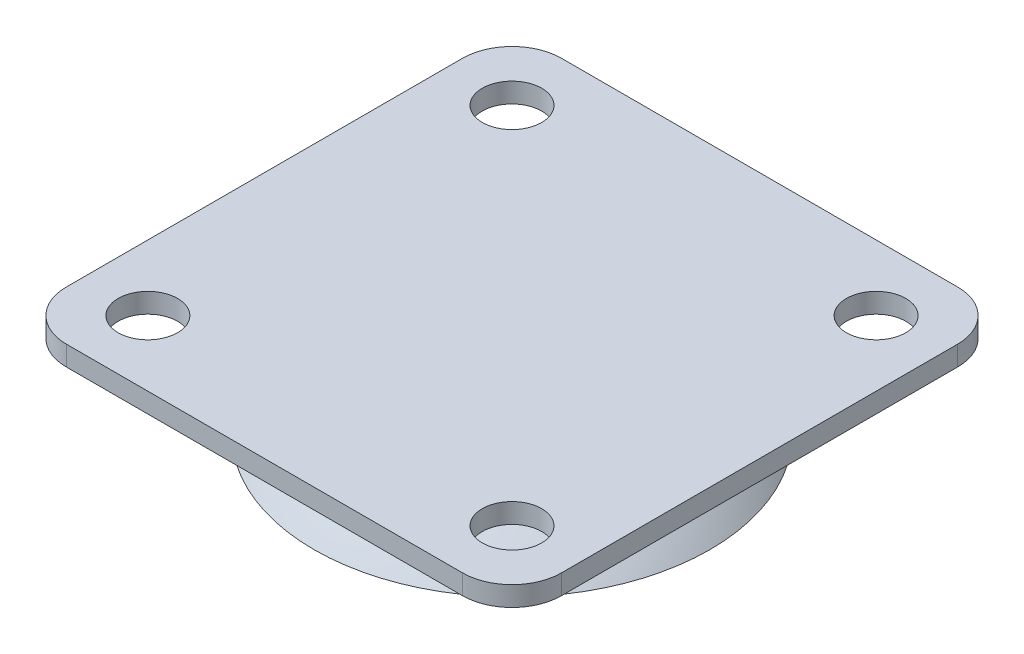
SolidWorks part; units mm, degrees
material "Chromium Copper, UNS C18200"
ref_plane "Front Plane" through (0, 0, 0) normal (0, 0, 1) x (1, 0, 0)
ref_plane "Top Plane" through (0, 0, 0) normal (0, 1, 0) x (1, 0, 0)
ref_plane "Right Plane" through (0, 0, 0) normal (1, 0, 0) x (0, 0, -1)
sketch "Sketch1" plane through (0, 0, 0) normal (0, 1, 0) x (1, 0, 0)
  line L0 (0, 37.0869) -> (0, -44.714) construction
  line L1 (-25, 25) -> (25, 25)
  line L2 (-25, 25) -> (-25, -25)
  line L3 (-25, -25) -> (25, -25)
  line L4 (25, 25) -> (25, -25)
  line L5 (-25, 25) -> (25, -25) construction
  line L6 (-25, -25) -> (25, 25) construction
  line L7 (28.9831, 0) -> (-36.8008, 0) construction
  circle A0 centre (18.3848, 18.3848) radius 3
  circle A1 centre (-18.3848, 18.3848) radius 3
  circle A2 centre (18.3848, -18.3848) radius 3
  circle A3 centre (-18.3848, -18.3848) radius 3
  point P0 (0, 0)
  dimension "D3" = 6
  dimension "D1" = 50
  dimension "D2" = 50
  dimension "D4" = 26
extrude "Boss-Extrude1" add sketch "Sketch1" along normal blind 2
sketch "Sketch2" plane through (0, 0, 0) normal (0, 0, 1) x (1, 0, 0)
  line L0 (0, 10.006) -> (0, -2.02) construction
  line L1 (0, 0) -> (0, -2.02)
  line L2 (20, -8.4681) -> (17.1604, -8.4681)
  line L3 (0, -2.9806) -> (0, -16.3725) construction
  line L4 (1.9993, -2.0726) -> (1.9993, -2.0726)
  line L5 (15.679, -7.1244) -> (15.679, -7.1244)
  line L6 (0, -2.02) -> (1.9993, -2.0726)
  line L7 (15.679, -7.1244) -> (17.1604, -8.4681)
  spline S0 degree 2 poles (0, 0) (12.4384, -0.0796) (20, -8.4681) knots 0 0 0 1 1 1
  spline S1 degree 1 poles (1.9993, -2.0726) (15.679, -7.1244) knots 0 0 1 1 construction
  spline S2 degree 3 poles (1.9993, -2.0726) (2.666, -2.1173) (4.014, -2.2516) (6.5495, -2.6834) (9.5254, -3.5338) (12.7654, -5.0356) (14.7494, -6.3804) (15.679, -7.1244) knots 0.087231 0.087231 0.087231 0.087231 0.177417 0.267603 0.447975 0.628347 0.808719 0.808719 0.808719 0.808719
  dimension "D1" = 20
  dimension "D2" = 2
revolve "Revolve1" add sketch "Sketch2" angle 360 about L0 region at (9.8663, -3.4389, 0)
fillet "Fillet1" radius 5 4 edges at (25, 1, 25) (-25, 1, 25) (-25, 1, -25) (25, 1, -25)
ref_axis "Axis1" through (18.3848, 2, -18.3848) along (0, -1, 0)
ref_axis "Axis2" through (-18.3848, 2, 18.3848) along (0, -1, 0)
